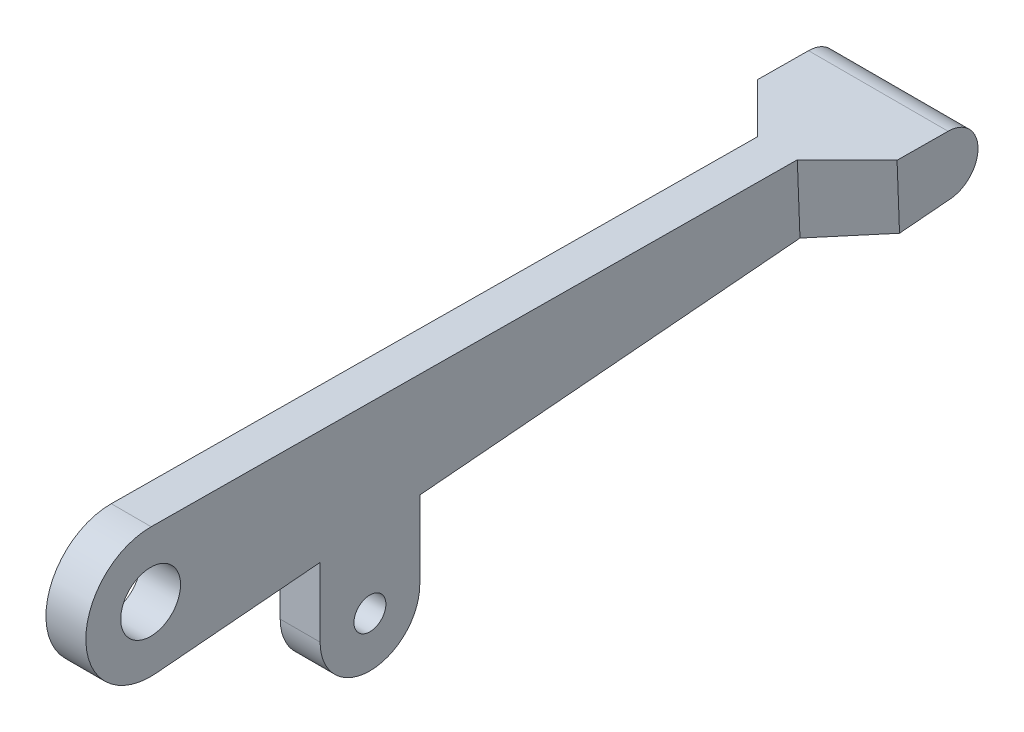
SolidWorks part; units mm, degrees
material "Tough 2000"
ref_plane "Front Plane" through (0, 0, 0) normal (0, 0, 1) x (1, 0, 0)
ref_plane "Top Plane" through (0, 0, 0) normal (0, 1, 0) x (1, 0, 0)
ref_plane "Right Plane" through (0, 0, 0) normal (1, 0, 0) x (0, 0, -1)
sketch "Sketch1" plane through (0, 0, 0) normal (1, 0, 0) x (0, 0, -1)
  line L3 (0.0534, 6.4998) -> (75, 5.8839)
  line L4 (0.5524, -6.4765) -> (17, -5.0737)
  line L5 (17, -12) -> (17, -5.0737)
  line L6 (27, -12) -> (27, -4.2208)
  line L7 (27, -4.2208) -> (75.2549, -0.1053)
  arc A0 (0.0534, 6.4998) -> (0.5524, -6.4765) centre (0, 0) ccw
  arc A1 (75.2549, -0.1053) -> (75, 5.8839) centre (75, 2.8839) ccw
  arc A2 (17, -12) -> (27, -12) centre (22, -12) ccw
  circle A3 centre (22, -12) radius 1.6
  circle A4 centre (0, 0) radius 3
  dimension "D1" = 75
  dimension "D2" = 12
  dimension "D4" = 6.5
  dimension "D5" = 3
  dimension "D6" = 5
  dimension "D3" = 22
extrude "Boss-Extrude1" add sketch "Sketch1" along normal blind 4
sketch "Sketch2" plane through (4, 0, 0) normal (1, 0, 0) x (0, 0, -1)
  line L0 (70.0037, 2.6918) -> (70.1281, -0.5425)
  line L2 (75, 2.8839) -> (70.0037, 2.6918) construction
  line L4 (70.0037, 2.6918) -> (69.8793, 5.926)
  line L5 (75, 5.8839) -> (0.0534, 6.4998) construction
  line L8 (27, -4.2208) -> (75.2549, -0.1053) construction
  line L9 (75.2549, -0.1053) -> (70.1281, -0.5425)
  line L10 (69.8793, 5.926) -> (75, 5.8839)
  arc A1 (75, 5.8839) -> (75.2549, -0.1053) centre (75, 2.8839) cw
extrude "Boss-Extrude2" add sketch "Sketch2" along normal blind 5 and the other way blind 9
chamfer "Chamfer1" distance 5 angle 45 2 edges at (0, 2.6917, -70.0037) (4, 2.6917, -70.0037)
